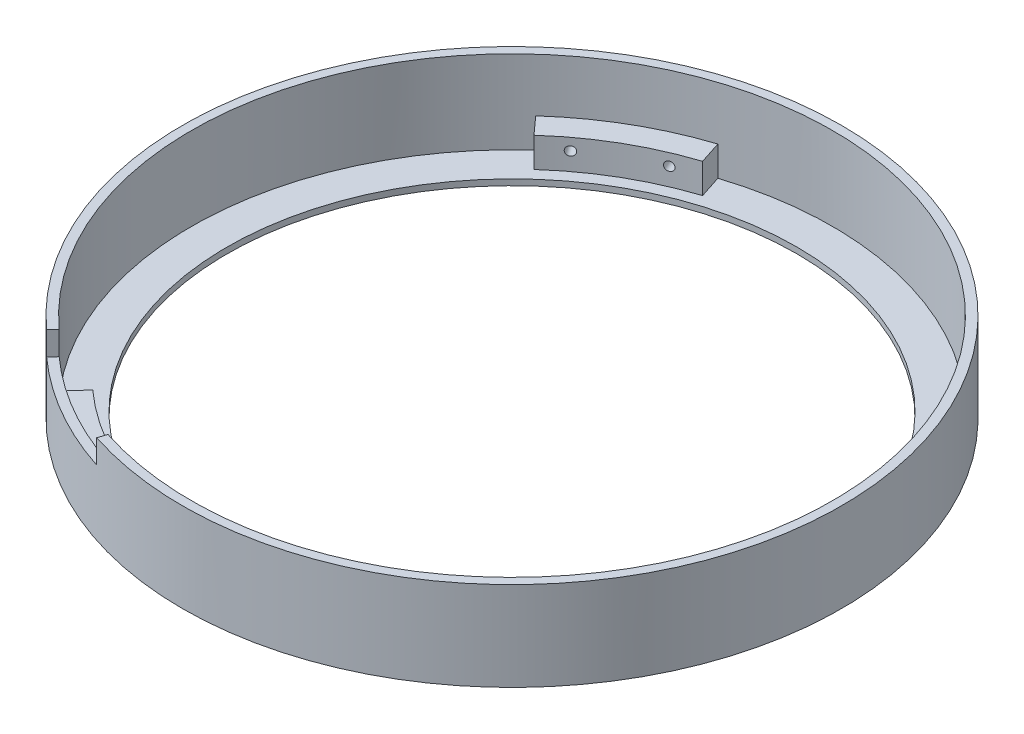
SolidWorks part; units mm, degrees
ref_plane "Front Plane" through (0, 0, 0) normal (0, 0, 1) x (1, 0, 0)
ref_plane "Top Plane" through (0, 0, 0) normal (0, 1, 0) x (1, 0, 0)
ref_plane "Right Plane" through (0, 0, 0) normal (1, 0, 0) x (0, 0, -1)
sketch "Sketch1" plane through (0, 0, 0) normal (0, 0, 1) x (1, 0, 0)
  line L0 (55.5, 11) -> (55.5, -4)
  line L1 (55.5, -4) -> (48, -4)
  line L2 (48, -4) -> (48, -3)
  line L3 (48, -3) -> (54, -3)
  line L4 (54, -3) -> (54, 11)
  line L5 (54, 11) -> (55.5, 11)
  line L6 (0, 0) -> (0, 7.9891)
  dimension "D1" = 15
  dimension "D2" = 1.5
  dimension "D3" = 1
  dimension "D4" = 55.5
  dimension "D5" = 7.5
  dimension "D6" = 4
revolve "Revolve1" add sketch "Sketch1" angle 360 about L6 region at (55.3323, 3.5, 0)
sketch "Sketch3" plane through (0, -3, 0) normal (0, 1, 0) x (1, 0, 0)
  line L0 (50, 0) -> (0, 0)
  line L1 (0, 0) -> (52.82, -11.2272)
  line L2 (0, 0) -> (52.82, 11.2272)
  line L3 (0, 0) -> (-16.6869, -51.3571)
  line L4 (0, 0) -> (-36.1331, -40.1298)
  line L5 (0, 0) -> (-36.1331, 40.1298)
  line L6 (0, 0) -> (-16.6869, 51.3571)
  circle A0 centre (0, 0) radius 54
  arc A1 (48.9074, -10.3956) -> (48.9074, 10.3956) centre (0, 0) ccw
  arc A3 (-33.4565, -37.1572) -> (-15.4508, -47.5528) centre (0, 0) ccw
  arc A4 (-15.4508, 47.5528) -> (-33.4565, 37.1572) centre (0, 0) ccw
  arc A5 (48.9074, -10.3956) -> (48.9074, 10.3956) centre (0, 0) ccw
  arc A6 (-15.4508, 47.5528) -> (-33.4565, 37.1572) centre (0, 0) ccw
  circle M11 centre (0, 0) radius 54
  dimension "D1" = 100
  dimension "D2" = 24
  dimension "D3" = 24
  dimension "D4" = 24
  dimension "D5" = 12
  dimension "D6" = 96
  dimension "D7" = 96
  dimension "D8" = 96
extrude "Boss-Extrude1" add sketch "Sketch3" along normal blind 5 contours L4 L3 M11 region at (-25.8231, -3, 44.7269)
extrude "Boss-Extrude2" add sketch "Sketch3<3>" along normal blind 5 contours A1 L1 L2 M11 region at (51.6461, -3, 0)
sketch "Sketch3<3>" plane through (0, -3, 0) normal (0, 1, 0) x (1, 0, 0) same geometry as "Sketch3"
extrude "Boss-Extrude3" add sketch "Sketch3<4>" along normal blind 5 contours A4 L6 L5 M11 region at (-25.8231, -3, -44.7269)
sketch "Sketch3<4>" plane through (0, -3, 0) normal (0, 1, 0) x (1, 0, 0) same geometry as "Sketch3"
sketch "Sketch7" plane through (0, 11, 0) normal (0, 1, 0) x (1, 0, 0)
  line L0 (0, 0) -> (-17.1504, -52.7836)
  line L1 (0, 0) -> (-37.1367, -41.2445)
  line L2 (0, 0) -> (55.5, 0)
  circle A0 centre (0, 0) radius 55.5 construction
  circle M4 centre (0, 0) radius 55.5
  circle M5 centre (0, 0) radius 54
  dimension "D1" = 24
  dimension "D2" = 108
hole_wizard "Ø1.5mm Dowel Hole1" positions "3DSketch1" profile "Sketch8" hole size "Ø1.5" standard "ANSI Metric"
sketch3d "3DSketch1"
  line L0 (0, 0, 0) -> (-19.5366, 0, 46.0252)
  line L2 (0, 0, 0) -> (-30.0908, 0, 39.9318)
  line L4 (0, 0, 0) -> (-19.5366, 0, -46.0252)
  line L6 (0, 0, 0) -> (-30.0908, 0, -39.9318)
  line L8 (49.6273, 0, 6.0935) -> (0, 0, 0)
  line L10 (49.6273, 0, -6.0935) -> (0, 0, 0)
  line L12 (48.9074, -3, 10.3956) -> (48.9074, 0, 10.3956)
  line L13 (48.9074, 2, 10.3956) -> (48.9074, -3, 10.3956) construction
  line L15 (48.9074, 0, 10.3956) -> (0, 0, 0)
  point P0 (-30.0908, 0, -39.9318)
  point P2 (-19.5366, 0, -46.0252)
  point P4 (49.6273, 0, -6.0935)
  point P6 (49.6273, 0, 6.0935)
  point P8 (-30.0908, 0, 39.9318)
  point P10 (-19.5366, 0, 46.0252)
  dimension "D1" = 4
  dimension "D2" = 4
  dimension "D3" = 4
  dimension "D4" = 4
  dimension "D5" = 4
  dimension "D6" = 4
  dimension "D7" = 3
  dimension "D8" = 5
  dimension "D9" = 14
  dimension "D10" = 14
  dimension "D11" = 14
  dimension "D12" = 106
  dimension "D13" = 106
  dimension "D14" = 106
sketch "Sketch8" plane through (-30.0908, 0, -39.9318) normal (0, 1, 0) x (0.7986, 0, -0.6018)
  line L0 (0, 0) -> (0, 3.4506)
  line L1 (0, 3.4506) -> (0.75, 3)
  line L2 (0.75, 3) -> (0.75, 0)
  line L5 (0.75, 0) -> (0, 0)
  line L10 (0, 3.4506) -> (-0.75, 3) construction
  line L11 (0, -6.35) -> (0, 107.95) construction
  dimension "Hole Dia." = 1.5
  dimension "Hole Depth" = 3
  dimension "Drill Angle" = 118
extrude "Cut-Extrude2" cut sketch "Sketch7" against normal blind 4 contours L1 L0 M5 M4 region at (-27.177, 11, 47.072)
